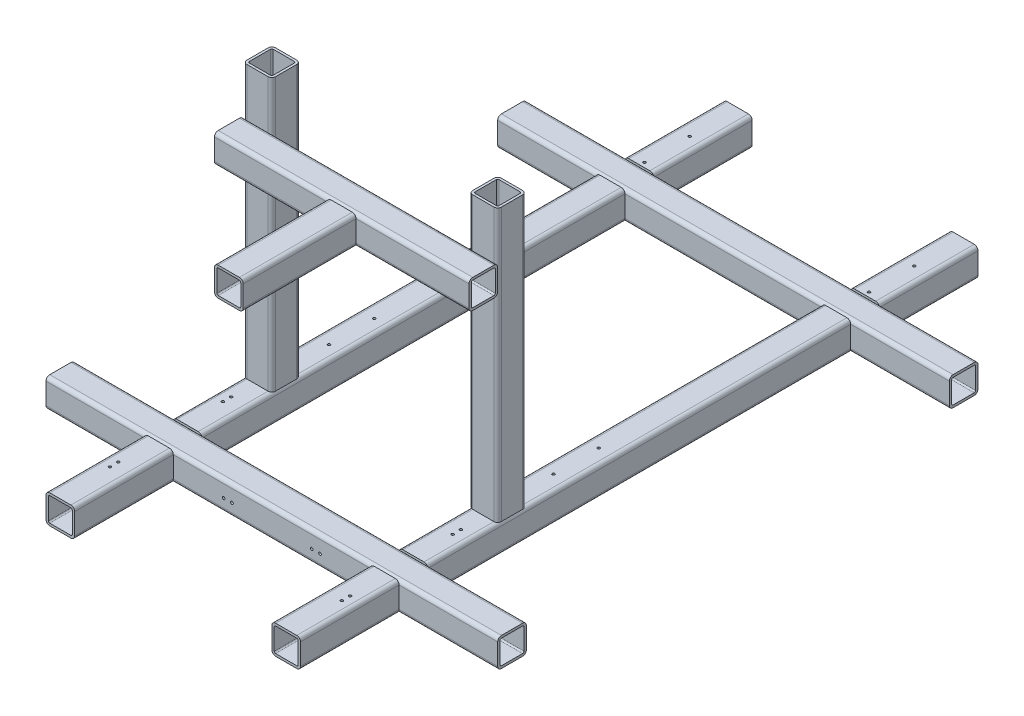
SolidWorks part; units mm, degrees
ref_plane "Front Plane" through (0, 0, 0) normal (0, 0, 1) x (1, 0, 0)
ref_plane "Top Plane" through (0, 0, 0) normal (0, 1, 0) x (1, 0, 0)
ref_plane "Right Plane" through (0, 0, 0) normal (1, 0, 0) x (0, 0, -1)
ref_plane "Bottom Face" through (0, 0, 0) normal (0, 1, 0) x (1, 0, 0)
ref_plane "Top Face" through (0, 38.1, 0) normal (0, 1, 0) x (1, 0, 0)
ref_plane "Mid Plane" through (0, 19.05, 0) normal (0, 1, 0) x (1, 0, 0)
ref_plane "Front Face" through (0, 0, 450) normal (0, 0, 1) x (1, 0, 0)
ref_plane "Back Face" through (0, 0, -450) normal (0, 0, 1) x (1, 0, 0)
ref_plane "Left Face" through (300, 0, 0) normal (1, 0, 0) x (0, 0, -1)
ref_plane "Right Face" through (-300, 0, 0) normal (1, 0, 0) x (0, 0, -1)
ref_plane "Divider Plane" through (0, 0, 150) normal (0, 0, 1) x (1, 0, 0)
ref_plane "Max Height Plane" through (0, 400, 0) normal (0, 1, 0) x (1, 0, 0)
ref_plane "Electronics Box Plane" through (0, 338.1, 0) normal (0, 1, 0) x (1, 0, 0)
sketch "Sketch2" plane through (300, 0, 0) normal (1, 0, 0) x (0, 0, -1)
  line L0 (330, 38.1) -> (-330, 38.1) construction
  line L5 (330, 0) -> (-330, 0) construction
  line L6 (0, 220) -> (0, -220) construction
  line L7 (-314.05, 38.1) -> (-285.95, 38.1)
  line L8 (-280.95, 33.1) -> (-280.95, 5)
  line L9 (-315.875, 33.1) -> (-315.875, 5)
  line L10 (-314.05, 3.175) -> (-285.95, 3.175)
  line L11 (-285.95, 0) -> (-314.05, 0)
  line L12 (-319.05, 5) -> (-319.05, 33.1)
  line L13 (-300, 38.1) -> (-300, 0) construction
  line L14 (-319.05, 19.05) -> (-280.95, 19.05) construction
  line L15 (-284.125, 5) -> (-284.125, 33.1)
  line L16 (-285.95, 34.925) -> (-314.05, 34.925)
  line L17 (-300, 34.925) -> (-300, 3.175) construction
  line L18 (-315.875, 19.05) -> (-284.125, 19.05) construction
  arc A0 (-285.95, 38.1) -> (-280.95, 33.1) centre (-285.95, 33.1) cw
  arc A1 (-280.95, 5) -> (-285.95, 0) centre (-285.95, 5) cw
  arc A2 (-314.05, 0) -> (-319.05, 5) centre (-314.05, 5) cw
  arc A3 (-319.05, 33.1) -> (-314.05, 38.1) centre (-314.05, 33.1) cw
  arc A4 (-315.875, 5) -> (-314.05, 3.175) centre (-314.05, 5) ccw
  arc A5 (-285.95, 3.175) -> (-284.125, 5) centre (-285.95, 5) ccw
  arc A6 (-284.125, 33.1) -> (-285.95, 34.925) centre (-285.95, 33.1) ccw
  arc A7 (-314.05, 34.925) -> (-315.875, 33.1) centre (-314.05, 33.1) ccw
  point P20 (-300, 19.05)
  point P39 (-300, 19.05)
  dimension "D1" = 5
  dimension "D2" = 300
  dimension "D3" = 3.175
extrude "Front Cross-Car Member" add sketch "Sketch2" against normal up to surface (600 mm away) up to plane "Right Face"
sketch "Sketch5" plane through (300, 0, 0) normal (1, 0, 0) x (0, 0, -1)
  line L0 (285.95, 38.1) -> (314.05, 38.1)
  line L1 (319.05, 33.1) -> (319.05, 5)
  line L2 (314.05, 0) -> (285.95, 0)
  line L3 (280.95, 5) -> (280.95, 33.1)
  line L4 (300, 38.1) -> (300, 0) construction
  line L5 (280.95, 19.05) -> (319.05, 19.05) construction
  line L6 (285.95, 34.925) -> (314.05, 34.925)
  line L7 (315.875, 33.1) -> (315.875, 5)
  line L8 (314.05, 3.175) -> (285.95, 3.175)
  line L9 (284.125, 5) -> (284.125, 33.1)
  line L10 (300, 34.925) -> (300, 3.175) construction
  line L11 (284.125, 19.05) -> (315.875, 19.05) construction
  line L12 (330, 0) -> (-330, 0) construction
  line L14 (330, 38.1) -> (-330, 38.1) construction
  line L15 (0, 220) -> (0, -220) construction
  arc A0 (314.05, 38.1) -> (319.05, 33.1) centre (314.05, 33.1) cw
  arc A1 (319.05, 5) -> (314.05, 0) centre (314.05, 5) cw
  arc A2 (285.95, 0) -> (280.95, 5) centre (285.95, 5) cw
  arc A3 (280.95, 33.1) -> (285.95, 38.1) centre (285.95, 33.1) cw
  arc A4 (314.05, 34.925) -> (315.875, 33.1) centre (314.05, 33.1) cw
  arc A5 (315.875, 5) -> (314.05, 3.175) centre (314.05, 5) cw
  arc A6 (285.95, 3.175) -> (284.125, 5) centre (285.95, 5) cw
  arc A7 (284.125, 33.1) -> (285.95, 34.925) centre (285.95, 33.1) cw
  point P32 (300, 19.05)
  point P33 (300, 19.05)
  dimension "D2" = 5
  dimension "D1" = 3.175
  dimension "D3" = 300
extrude "Back Cross-Car Member" add sketch "Sketch5" against normal up to surface (600 mm away) separate body up to plane "Right Face"
sketch "Sketch6" plane through (0, 0, -450) normal (0, 0, 1) x (1, 0, 0)
  line L0 (135.95, 38.1) -> (164.05, 38.1)
  line L1 (169.05, 33.1) -> (169.05, 5)
  line L2 (134.125, 33.1) -> (134.125, 5)
  line L3 (135.95, 3.175) -> (164.05, 3.175)
  line L4 (164.05, 0) -> (135.95, 0)
  line L5 (130.95, 5) -> (130.95, 33.1)
  line L6 (150, 38.1) -> (150, 0) construction
  line L7 (130.95, 19.05) -> (169.05, 19.05) construction
  line L8 (165.875, 5) -> (165.875, 33.1)
  line L9 (164.05, 34.925) -> (135.95, 34.925)
  line L10 (150, 34.925) -> (150, 3.175) construction
  line L11 (134.125, 19.05) -> (165.875, 19.05) construction
  line L12 (330, 38.1) -> (-330, 38.1) construction
  line L13 (330, 0) -> (-330, 0) construction
  line L14 (0, -220) -> (0, 220) construction
  arc A0 (164.05, 38.1) -> (169.05, 33.1) centre (164.05, 33.1) cw
  arc A1 (169.05, 5) -> (164.05, 0) centre (164.05, 5) cw
  arc A2 (135.95, 0) -> (130.95, 5) centre (135.95, 5) cw
  arc A3 (130.95, 33.1) -> (135.95, 38.1) centre (135.95, 33.1) cw
  arc A4 (134.125, 5) -> (135.95, 3.175) centre (135.95, 5) ccw
  arc A5 (164.05, 3.175) -> (165.875, 5) centre (164.05, 5) ccw
  arc A6 (165.875, 33.1) -> (164.05, 34.925) centre (164.05, 33.1) ccw
  arc A7 (135.95, 34.925) -> (134.125, 33.1) centre (135.95, 33.1) ccw
  point P16 (150, 19.05)
  point P33 (150, 19.05)
  dimension "D1" = 5
  dimension "D2" = 3.175
  dimension "D3" = 150
extrude "Back Left Along-Car Member" add sketch "Sketch6" along normal blind 130.95
extrude "Middle Left Along-Car Member" add sketch "Sketch6<2>" along normal blind 561.9 from offset 169.05
sketch "Sketch6<2>" plane through (0, 0, -450) normal (0, 0, 1) x (1, 0, 0) same geometry as "Sketch6"
extrude "Front Left Along-Car Member" add sketch "Sketch6<3>" along normal blind 130.95 from offset 769.05
sketch "Sketch6<3>" plane through (0, 0, -450) normal (0, 0, 1) x (1, 0, 0) same geometry as "Sketch6"
sketch "Sketch7" plane through (0, 0, -450) normal (0, 0, 1) x (1, 0, 0)
  line L0 (-164.05, 38.1) -> (-135.95, 38.1)
  line L1 (-130.95, 33.1) -> (-130.95, 5)
  line L2 (-165.875, 33.1) -> (-165.875, 5)
  line L3 (-164.05, 3.175) -> (-135.95, 3.175)
  line L4 (-135.95, 0) -> (-164.05, 0)
  line L5 (-169.05, 5) -> (-169.05, 33.1)
  line L6 (-150, 38.1) -> (-150, 0) construction
  line L7 (-169.05, 19.05) -> (-130.95, 19.05) construction
  line L8 (-134.125, 5) -> (-134.125, 33.1)
  line L9 (-135.95, 34.925) -> (-164.05, 34.925)
  line L10 (-150, 34.925) -> (-150, 3.175) construction
  line L11 (-165.875, 19.05) -> (-134.125, 19.05) construction
  line L12 (330, 38.1) -> (-330, 38.1) construction
  line L13 (330, 0) -> (-330, 0) construction
  line L14 (0, -220) -> (0, 220) construction
  arc A0 (-135.95, 38.1) -> (-130.95, 33.1) centre (-135.95, 33.1) cw
  arc A1 (-130.95, 5) -> (-135.95, 0) centre (-135.95, 5) cw
  arc A2 (-164.05, 0) -> (-169.05, 5) centre (-164.05, 5) cw
  arc A3 (-169.05, 33.1) -> (-164.05, 38.1) centre (-164.05, 33.1) cw
  arc A4 (-165.875, 5) -> (-164.05, 3.175) centre (-164.05, 5) ccw
  arc A5 (-135.95, 3.175) -> (-134.125, 5) centre (-135.95, 5) ccw
  arc A6 (-134.125, 33.1) -> (-135.95, 34.925) centre (-135.95, 33.1) ccw
  arc A7 (-164.05, 34.925) -> (-165.875, 33.1) centre (-164.05, 33.1) ccw
  point P16 (-150, 19.05)
  point P33 (-150, 19.05)
  dimension "D1" = 5
  dimension "D2" = 3.175
  dimension "D3" = 150
extrude "Back Right Along-Car Member" add sketch "Sketch7" along normal blind 130.95
extrude "Middle Right Along-Car Member" add sketch "Sketch7<2>" along normal blind 561.9 from offset 169.05
sketch "Sketch7<2>" plane through (0, 0, -450) normal (0, 0, 1) x (1, 0, 0) same geometry as "Sketch7"
extrude "Front Right Along-Car Member" add sketch "Sketch7<3>" along normal blind 130.95 from offset 769.05
sketch "Sketch7<3>" plane through (0, 0, -450) normal (0, 0, 1) x (1, 0, 0) same geometry as "Sketch7"
sketch "Sketch8" plane through (0, 38.1, 0) normal (0, 1, 0) x (1, 0, 0)
  line L0 (-164.05, -150) -> (-135.95, -150)
  line L1 (-130.95, -155) -> (-130.95, -183.1)
  line L2 (-165.875, -155) -> (-165.875, -183.1)
  line L3 (-164.05, -184.925) -> (-135.95, -184.925)
  line L4 (-135.95, -188.1) -> (-164.05, -188.1)
  line L5 (-169.05, -183.1) -> (-169.05, -155)
  line L6 (-150, -150) -> (-150, -188.1) construction
  line L7 (-169.05, -169.05) -> (-130.95, -169.05) construction
  line L8 (-134.125, -183.1) -> (-134.125, -155)
  line L9 (-135.95, -153.175) -> (-164.05, -153.175)
  line L10 (-150, -153.175) -> (-150, -184.925) construction
  line L11 (-165.875, -169.05) -> (-134.125, -169.05) construction
  line L12 (-220, -150) -> (220, -150) construction
  line L13 (0, -220) -> (0, 220) construction
  arc A0 (-135.95, -150) -> (-130.95, -155) centre (-135.95, -155) cw
  arc A1 (-130.95, -183.1) -> (-135.95, -188.1) centre (-135.95, -183.1) cw
  arc A2 (-164.05, -188.1) -> (-169.05, -183.1) centre (-164.05, -183.1) cw
  arc A3 (-169.05, -155) -> (-164.05, -150) centre (-164.05, -155) cw
  arc A4 (-165.875, -183.1) -> (-164.05, -184.925) centre (-164.05, -183.1) ccw
  arc A5 (-135.95, -184.925) -> (-134.125, -183.1) centre (-135.95, -183.1) ccw
  arc A6 (-134.125, -155) -> (-135.95, -153.175) centre (-135.95, -155) ccw
  arc A7 (-164.05, -153.175) -> (-165.875, -155) centre (-164.05, -155) ccw
  point P16 (-150, -169.05)
  point P33 (-150, -169.05)
  dimension "D1" = 5
  dimension "D2" = 3.175
  dimension "D3" = 38.1
  dimension "D4" = 150
extrude "Right Vertical Member" add sketch "Sketch8" along normal up to surface (361.9 mm away) up to plane "Max Height Plane"
sketch "Sketch10" plane through (0, 38.1, 0) normal (0, 1, 0) x (1, 0, 0)
  line L0 (135.95, -150) -> (164.05, -150)
  line L1 (169.05, -155) -> (169.05, -183.1)
  line L2 (134.125, -155) -> (134.125, -183.1)
  line L3 (135.95, -184.925) -> (164.05, -184.925)
  line L4 (164.05, -188.1) -> (135.95, -188.1)
  line L5 (130.95, -183.1) -> (130.95, -155)
  line L6 (150, -150) -> (150, -188.1) construction
  line L7 (130.95, -169.05) -> (169.05, -169.05) construction
  line L8 (165.875, -183.1) -> (165.875, -155)
  line L9 (164.05, -153.175) -> (135.95, -153.175)
  line L10 (150, -153.175) -> (150, -184.925) construction
  line L11 (134.125, -169.05) -> (165.875, -169.05) construction
  line L12 (-220, -150) -> (220, -150) construction
  line L13 (0, -220) -> (0, 220) construction
  arc A0 (164.05, -150) -> (169.05, -155) centre (164.05, -155) cw
  arc A1 (169.05, -183.1) -> (164.05, -188.1) centre (164.05, -183.1) cw
  arc A2 (135.95, -188.1) -> (130.95, -183.1) centre (135.95, -183.1) cw
  arc A3 (130.95, -155) -> (135.95, -150) centre (135.95, -155) cw
  arc A4 (134.125, -183.1) -> (135.95, -184.925) centre (135.95, -183.1) ccw
  arc A5 (164.05, -184.925) -> (165.875, -183.1) centre (164.05, -183.1) ccw
  arc A6 (165.875, -155) -> (164.05, -153.175) centre (164.05, -155) ccw
  arc A7 (135.95, -153.175) -> (134.125, -155) centre (135.95, -155) ccw
  point P16 (150, -169.05)
  point P33 (150, -169.05)
  dimension "D1" = 5
  dimension "D2" = 3.175
  dimension "D3" = 38.1
  dimension "D4" = 150
extrude "Left Vertical Member" add sketch "Sketch10" along normal up to surface (361.9 mm away) up to plane "Max Height Plane"
sketch "Sketch11" plane through (300, 0, 0) normal (1, 0, 0) x (0, 0, -1)
  line L0 (-221.2, 338.1) -> (-193.1, 338.1)
  line L1 (-188.1, 333.1) -> (-188.1, 305)
  line L2 (-223.025, 333.1) -> (-223.025, 305)
  line L3 (-221.2, 303.175) -> (-193.1, 303.175)
  line L4 (-193.1, 300) -> (-221.2, 300)
  line L5 (-226.2, 305) -> (-226.2, 333.1)
  line L6 (-207.15, 338.1) -> (-207.15, 300) construction
  line L7 (-226.2, 319.05) -> (-188.1, 319.05) construction
  line L8 (-191.275, 305) -> (-191.275, 333.1)
  line L9 (-193.1, 334.925) -> (-221.2, 334.925)
  line L10 (-207.15, 334.925) -> (-207.15, 303.175) construction
  line L11 (-223.025, 319.05) -> (-191.275, 319.05) construction
  line L12 (-150, 220) -> (-150, -220) construction
  line L13 (330, 338.1) -> (-330, 338.1) construction
  arc A0 (-193.1, 338.1) -> (-188.1, 333.1) centre (-193.1, 333.1) cw
  arc A1 (-188.1, 305) -> (-193.1, 300) centre (-193.1, 305) cw
  arc A2 (-221.2, 300) -> (-226.2, 305) centre (-221.2, 305) cw
  arc A3 (-226.2, 333.1) -> (-221.2, 338.1) centre (-221.2, 333.1) cw
  arc A4 (-223.025, 305) -> (-221.2, 303.175) centre (-221.2, 305) ccw
  arc A5 (-193.1, 303.175) -> (-191.275, 305) centre (-193.1, 305) ccw
  arc A6 (-191.275, 333.1) -> (-193.1, 334.925) centre (-193.1, 333.1) ccw
  arc A7 (-221.2, 334.925) -> (-223.025, 333.1) centre (-221.2, 333.1) ccw
  point P16 (-207.15, 319.05)
  point P33 (-207.15, 319.05)
  dimension "D1" = 5
  dimension "D2" = 3.175
  dimension "D3" = 38.1
  dimension "D4" = 38.1
extrude "Upper Cross-Car Member" add sketch "Sketch11" against normal blind 338.1 from offset 130.95 offset against normal yes
sketch "Sketch12" plane through (0, 0, 150) normal (0, 0, 1) x (1, 0, 0)
  line L0 (-14.05, 338.1) -> (14.05, 338.1)
  line L1 (19.05, 333.1) -> (19.05, 305)
  line L2 (-15.875, 333.1) -> (-15.875, 305)
  line L3 (-14.05, 303.175) -> (14.05, 303.175)
  line L4 (14.05, 300) -> (-14.05, 300)
  line L5 (-19.05, 305) -> (-19.05, 333.1)
  line L6 (0, 338.1) -> (0, 300) construction
  line L7 (-19.05, 319.05) -> (19.05, 319.05) construction
  line L8 (15.875, 305) -> (15.875, 333.1)
  line L9 (14.05, 334.925) -> (-14.05, 334.925)
  line L10 (0, 334.925) -> (0, 303.175) construction
  line L11 (-15.875, 319.05) -> (15.875, 319.05) construction
  line L12 (330, 338.1) -> (-330, 338.1) construction
  line L13 (0, -220) -> (0, 220) construction
  arc A0 (14.05, 338.1) -> (19.05, 333.1) centre (14.05, 333.1) cw
  arc A1 (19.05, 305) -> (14.05, 300) centre (14.05, 305) cw
  arc A2 (-14.05, 300) -> (-19.05, 305) centre (-14.05, 305) cw
  arc A3 (-19.05, 333.1) -> (-14.05, 338.1) centre (-14.05, 333.1) cw
  arc A4 (-15.875, 305) -> (-14.05, 303.175) centre (-14.05, 305) ccw
  arc A5 (14.05, 303.175) -> (15.875, 305) centre (14.05, 305) ccw
  arc A6 (15.875, 333.1) -> (14.05, 334.925) centre (14.05, 333.1) ccw
  arc A7 (-14.05, 334.925) -> (-15.875, 333.1) centre (-14.05, 333.1) ccw
  point P16 (0, 319.05)
  point P33 (0, 319.05)
  dimension "D1" = 5
  dimension "D2" = 3.175
  dimension "D3" = 38.1
extrude "E-Box Platform Base" add sketch "Sketch12" along normal blind 150 from offset 76.2
sketch "Water Tank Mount Holes" plane through (0, 38.1, 0) normal (0, 1, 0) x (1, 0, 0)
  point P0 (-149.13, -93.95)
  point P1 (-149.13, -33.95)
  point P3 (149.13, -93.95)
  point P4 (149.13, -33.95)
  point P5 (149.13, 325.13)
  point P9 (149.13, 385.13)
  point P11 (-149.13, 325.13)
  point P13 (-149.13, 385.13)
hole_wizard "M3 Clearance Hole2" positions "Sketch14" profile "Sketch15" hole size "M3" standard "ANSI Metric" end condition through all
sketch "Sketch14" plane through (0, 38.1, 0) normal (0, 1, 0) x (1, 0, 0)
  point P0 (-149.13, -33.95)
  point P3 (-149.13, -93.95)
  point P6 (149.13, -93.95)
  point P9 (149.13, -33.95)
  point P12 (149.13, 325.13)
  point P15 (149.13, 385.13)
  point P18 (-149.13, 385.13)
  point P21 (-149.13, 325.13)
sketch "Sketch15" plane through (-149.13, 38.1, 33.95) normal (1, 0, 0) x (0, 0, 1)
  line L0 (0, 0) -> (0, 38.1)
  line L1 (0, 38.1) -> (1.7, 38.1)
  line L2 (1.7, 38.1) -> (1.7, 0)
  line L5 (1.7, 0) -> (0, 0)
  line L11 (0, -6.35) -> (0, 107.95) construction
  dimension "Thru Hole Dia." = 3.4
  dimension "Thru Hole Depth" = 38.1
sketch "Battery Top Mount Holes" plane through (0, 38.1, 0) normal (0, 1, 0) x (1, 0, 0)
  point P0 (-154.025, -369.1)
  point P1 (-154.025, -380.1)
  point P3 (-154.025, -230.1)
  point P5 (-154.025, -219.1)
  point P7 (154.025, -380.1)
  point P9 (154.025, -369.1)
  point P11 (151.325, -219.1)
  point P13 (151.325, -230.1)
  point P15 (0, 0)
  point P17 (-154.5168, -230.1)
  point P18 (-154.025, -230.1)
  point P20 (0, 0)
  point P21 (-154.025, -219.1)
  point P23 (0, 0)
  point P24 (151.325, -230.1)
  point P26 (0, 0)
  point P27 (154.025, -369.1)
sketch "Battery Bottom Mount Holes" plane through (0, 0, 319.05) normal (0, 0, 1) x (1, 0, 0)
  point P0 (63.95, 16.575)
  point P1 (52.95, 16.575)
  point P3 (-52.95, 16.575)
  point P5 (-63.95, 16.575)
  point P7 (0, 0)
  point P9 (-63.95, 16.575)
  point P11 (0, 0)
  point P12 (-52.95, 16.575)
  point P14 (0, 0)
  point P15 (52.95, 16.575)
  point P17 (0, 0)
  point P18 (63.95, 16.575)
hole_wizard "M3 Clearance Hole3" positions "Sketch18" profile "Sketch20" hole size "M3" standard "ANSI Metric" end condition through all
sketch "Sketch18" plane through (0, 38.1, 0) normal (0, 1, 0) x (1, 0, 0)
  point P0 (-154.025, -380.1)
  point P3 (-154.025, -369.1)
  point P6 (-154.025, -230.1)
  point P9 (-154.025, -219.1)
  point P12 (154.025, -380.1)
  point P15 (154.025, -369.1)
  point P18 (151.325, -230.1)
  point P21 (151.325, -219.1)
sketch "Sketch20" plane through (-154.025, 38.1, 380.1) normal (1, 0, 0) x (0, 0, 1)
  line L0 (0, 0) -> (0, 38.1)
  line L1 (0, 38.1) -> (1.7, 38.1)
  line L2 (1.7, 38.1) -> (1.7, 0)
  line L5 (1.7, 0) -> (0, 0)
  line L11 (0, -6.35) -> (0, 107.95) construction
  dimension "Thru Hole Dia." = 3.4
  dimension "Thru Hole Depth" = 38.1
hole_wizard "M3 Clearance Hole4" positions "Sketch21" profile "Sketch23" hole size "M3" standard "ANSI Metric"
sketch "Sketch21" plane through (0, 0, 319.05) normal (0, 0, 1) x (1, 0, 0)
  point P0 (-63.95, 16.575)
  point P3 (-52.95, 16.575)
  point P6 (52.95, 16.575)
  point P9 (63.95, 16.575)
sketch "Sketch23" plane through (-63.95, 16.575, 319.05) normal (1, 0, 0) x (0, -1, 0)
  line L0 (0, 0) -> (0, 39.1815)
  line L1 (0, 39.1815) -> (1.8, 38.1)
  line L2 (1.8, 38.1) -> (1.8, 0)
  line L5 (1.8, 0) -> (0, 0)
  line L10 (0, 39.1815) -> (-1.8, 38.1) construction
  line L11 (0, -6.35) -> (0, 107.95) construction
  dimension "Hole Dia." = 3.6
  dimension "Hole Depth" = 38.1
  dimension "Drill Angle" = 118
equation "\"D1@Front Face\" = \"frameLength@Master Assembly.SLDASM\" / 2"
equation "\"D1@Back Face\" = \"frameLength@Master Assembly.SLDASM\" / 2"
equation "\"D1@Left Face\"=\"frameWidth@Master Assembly.SLDASM\"/2"
equation "\"D1@Right Face\" = \"frameWidth@Master Assembly.SLDASM\" / 2"
equation "\"D1@Top Face\"=\"frameTubeStockHeight@Master Assembly.SLDASM\""
equation "\"D2@Sketch2\"=\"frameMemberDistLength@Master Assembly.SLDASM\"/2"
equation "\"D3@Sketch2\"=\"frameTubeStockWallThickness@Master Assembly.SLDASM\""
equation "\"D1@Sketch5\"=\"frameTubeStockWallThickness@Master Assembly.SLDASM\""
equation "\"D3@Sketch5\"=\"frameMemberDistLength@Master Assembly.SLDASM\"/2"
equation "\"D3@Sketch6\"=\"frameMemberDistWidth@Master Assembly.SLDASM\"/2"
equation "\"D1@Back Left Along-Car Member\"=(\"frameLength@Master Assembly.SLDASM\" - \"frameMemberDistLength@Master Assembly.SLDASM\" - \"frameTubeStockHeight@Master Assembly.SLDASM\")  / 2"
equation "\"D19@Middle Left Along-Car Member\" = ( \"frameLength@Master Assembly.SLDASM\" - \"frameMemberDistLength@Master Assembly.SLDASM\" + \"frameTubeStockHeight@Master Assembly.SLDASM\" ) / 2"
equation "\"D1@Middle Left Along-Car Member\"=\"frameMemberDistLength@Master Assembly.SLDASM\" - \"frameTubeStockHeight@Master Assembly.SLDASM\""
equation "\"D19@Front Left Along-Car Member\"=( \"frameLength@Master Assembly.SLDASM\" - \"frameMemberDistLength@Master Assembly.SLDASM\" )  / 2 + \"frameMemberDistLength@Master Assembly.SLDASM\" + \"frameTubeStockHeight@Master Assembly.SLDASM\" / 2"
equation "\"D1@Front Left Along-Car Member\"=(\"frameLength@Master Assembly.SLDASM\" - \"frameMemberDistLength@Master Assembly.SLDASM\" - \"frameTubeStockHeight@Master Assembly.SLDASM\")  / 2"
equation "\"D3@Sketch7\"=\"frameMemberDistWidth@Master Assembly.SLDASM\"/2"
equation "\"D1@Back Right Along-Car Member\"=(\"frameLength@Master Assembly.SLDASM\" - \"frameMemberDistLength@Master Assembly.SLDASM\" - \"frameTubeStockHeight@Master Assembly.SLDASM\")  / 2"
equation "\"D19@Middle Right Along-Car Member\" = ( \"frameLength@Master Assembly.SLDASM\" - \"frameMemberDistLength@Master Assembly.SLDASM\" + \"frameTubeStockHeight@Master Assembly.SLDASM\" ) / 2"
equation "\"D1@Middle Right Along-Car Member\"=\"frameMemberDistLength@Master Assembly.SLDASM\" - \"frameTubeStockHeight@Master Assembly.SLDASM\""
equation "\"D19@Front Right Along-Car Member\"=( \"frameLength@Master Assembly.SLDASM\" - \"frameMemberDistLength@Master Assembly.SLDASM\" )  / 2 + \"frameMemberDistLength@Master Assembly.SLDASM\" + \"frameTubeStockHeight@Master Assembly.SLDASM\" / 2"
equation "\"D1@Front Right Along-Car Member\"=(\"frameLength@Master Assembly.SLDASM\" - \"frameMemberDistLength@Master Assembly.SLDASM\" - \"frameTubeStockHeight@Master Assembly.SLDASM\")  / 2"
equation "\"D1@Divider Plane\"= \"frameDividerPlaneOffset@Master Assembly.SLDASM\""
equation "\"D3@Sketch8\"=\"frameTubeStockHeight@Master Assembly.SLDASM\""
equation "\"D4@Sketch8\"=\"frameMemberDistWidth@Master Assembly.SLDASM\"/2"
equation "\"D1@Max Height Plane\" = \"frameHeight@Master Assembly.SLDASM\""
equation "\"D4@Sketch10\"=\"frameMemberDistWidth@Master Assembly.SLDASM\"/2"
equation "\"D1@Electronics Box Plane\" = \"eboxPlaneHeight@Master Assembly.SLDASM\""
equation "\"D4@Sketch11\"=\"frameTubeStockHeight@Master Assembly.SLDASM\""
equation "\"D19@Upper Cross-Car Member\" = ( \"frameWidth@Master Assembly.SLDASM\" - \"frameMemberDistWidth@Master Assembly.SLDASM\" - \"frameTubeStockHeight@Master Assembly.SLDASM\" ) / 2"
equation "\"D1@Upper Cross-Car Member\" = \"frameMemberDistWidth@Master Assembly.SLDASM\" + \"frameTubeStockHeight@Master Assembly.SLDASM\""
equation "\"D19@E-Box Platform Base\"= \"frameTubeStockHeight@Master Assembly.SLDASM\" * 2"
equation "\"D2@Sketch6\"=\"frameTubeStockWallThickness@Master Assembly.SLDASM\""
equation "\"D2@Sketch7\"=\"frameTubeStockWallThickness@Master Assembly.SLDASM\""
equation "\"D2@Sketch8\"=\"frameTubeStockWallThickness@Master Assembly.SLDASM\""
equation "\"D3@Sketch10\"=\"frameTubeStockHeight@Master Assembly.SLDASM\""
equation "\"D2@Sketch10\"=\"frameTubeStockWallThickness@Master Assembly.SLDASM\""
equation "\"D3@Sketch11\"=\"frameTubeStockHeight@Master Assembly.SLDASM\""
equation "\"D2@Sketch11\"=\"frameTubeStockWallThickness@Master Assembly.SLDASM\""
equation "\"D3@Sketch12\"=\"frameTubeStockHeight@Master Assembly.SLDASM\""
equation "\"D2@Sketch12\"=\"frameTubeStockWallThickness@Master Assembly.SLDASM\""
